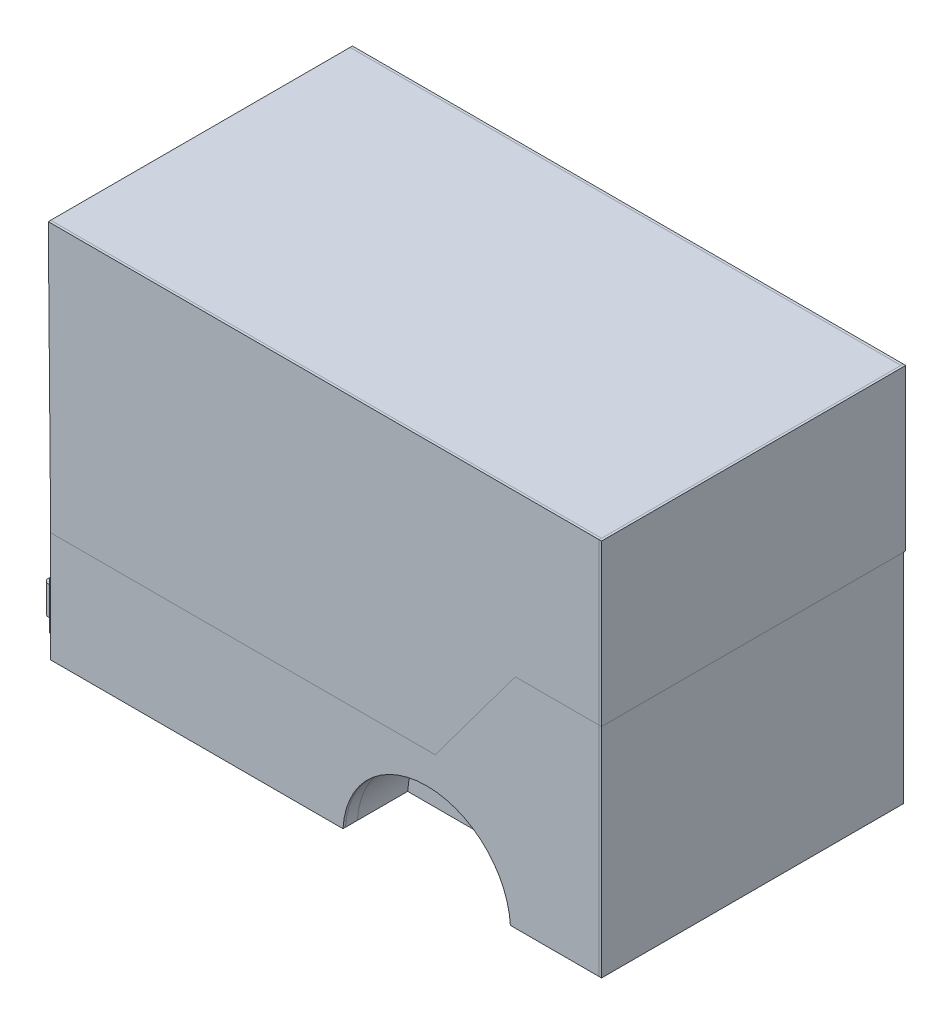
SolidWorks part; units mm, degrees
other "베이스 모듈"
other "결합장치1"
other "측벽"
other "결합장치2"
other "뒷벽인테리어(하양)"
other "뒷벽인테리어(검정)"
other "측벽인테리어(하양)2"
other "측벽인테리어(검정)2"
other "측벽인테리어(검정)1"
other "측벽인테리어(하양)1"
other "뒷벽"
other "천장"
other "뒷면벽"
other "측면벽"
other "침대"
other "베개"
other "이불"
other "싱크대"
other "인덕션"
other "인덕션 불판"
other "인덕션 다이얼"
other "후드"
other "수전"
other "천장수납"
other "천장수납1"
other "천장수납2"
other "천장수납3"
other "천장수납4"
other "부엌싱크"
other "세탁기"
other "세탁기_다이얼"
other "세탁기_스크린_1"
other "세탁기_스크린_2"
other "세탁기 링"
other "냉장고"
other "TV"
other "옷장"
other "탁자"
ref_plane "정면" through (0, 0, 0) normal (0, 0, 1) x (1, 0, 0)
ref_plane "윗면" through (0, 0, 0) normal (0, 1, 0) x (1, 0, 0)
ref_plane "우측면" through (0, 0, 0) normal (1, 0, 0) x (0, 0, -1)
sketch "스케치1" plane through (0, 0, 0) normal (0, 1, 0) x (1, 0, 0)
  line L1 (-757.2313, -2.0205) -> (-986.2313, -2.0205)
  line L2 (-757.2313, -2.0205) -> (-757.2313, -127.0205)
  line L3 (-757.2313, -127.0205) -> (-986.2313, -127.0205)
  line L4 (-986.2313, -2.0205) -> (-986.2313, -127.0205)
extrude "보스-돌출1" add sketch "스케치1" along normal up to surface (88 mm away)
sketch "스케치4" plane through (-986.2313, 0, 0) normal (-1, 0, 0) x (0, 0, 1)
  line L4 (2.0205, 0) -> (127.0205, 0)
  line L5 (2.0205, 88) -> (2.0205, 0)
  line L6 (127.0205, 88) -> (2.0205, 88)
  line L7 (127.0205, 0) -> (127.0205, 88)
  line L8 (123.0205, 84) -> (6.0205, 84)
  line L9 (123.0205, 67.306) -> (123.0205, 84)
  line L10 (120.1014, 42.8854) -> (120.8975, 46.7066)
  line L11 (118.0205, 2) -> (118.0205, 22.694)
  line L12 (11.0205, 2) -> (118.0205, 2)
  line L13 (11.0205, 22.694) -> (11.0205, 2)
  line L14 (8.1434, 46.7066) -> (8.9395, 42.8854)
  line L15 (6.0205, 84) -> (6.0205, 67.306)
  line L16 (123.0205, 84) -> (6.0205, 84)
  line L17 (123.0205, 67.306) -> (123.0205, 84)
  line L18 (120.1014, 42.8854) -> (120.8975, 46.7066)
  line L19 (118.0205, 2) -> (118.0205, 22.694)
  line L20 (11.0205, 2) -> (118.0205, 2)
  line L21 (11.0205, 22.694) -> (11.0205, 2)
  line L22 (8.1434, 46.7066) -> (8.9395, 42.8854)
  line L23 (6.0205, 84) -> (6.0205, 67.306)
  line L24 (117.0205, 3) -> (117.0205, 22.694)
  line L25 (119.1224, 43.0894) -> (119.9185, 46.9106)
  line L26 (122.0205, 67.306) -> (122.0205, 83)
  line L27 (122.0205, 83) -> (7.0205, 83)
  line L28 (7.0205, 83) -> (7.0205, 67.306)
  line L29 (9.1224, 46.9106) -> (9.9185, 43.0894)
  line L30 (12.0205, 22.694) -> (12.0205, 3)
  line L31 (12.0205, 3) -> (117.0205, 3)
  line L32 (117.0205, 3) -> (117.0205, 22.694)
  line L33 (119.1224, 43.0894) -> (119.9185, 46.9106)
  line L34 (122.0205, 67.306) -> (122.0205, 83)
  line L35 (122.0205, 83) -> (7.0205, 83)
  line L36 (7.0205, 83) -> (7.0205, 67.306)
  line L37 (9.1224, 46.9106) -> (9.9185, 43.0894)
  line L38 (12.0205, 22.694) -> (12.0205, 3)
  line L39 (12.0205, 3) -> (117.0205, 3)
  line L40 (2.0205, 0) -> (127.0205, 0)
  line L41 (2.0205, 88) -> (2.0205, 0)
  line L42 (127.0205, 88) -> (2.0205, 88)
  line L43 (127.0205, 0) -> (127.0205, 88)
  line L44 (126.0205, 1) -> (126.0205, 87)
  line L45 (3.0205, 1) -> (126.0205, 1)
  line L46 (3.0205, 87) -> (3.0205, 1)
  line L47 (126.0205, 87) -> (3.0205, 87)
  line L48 (126.0205, 1) -> (126.0205, 87)
  line L49 (3.0205, 1) -> (126.0205, 1)
  line L50 (3.0205, 87) -> (3.0205, 1)
  line L51 (126.0205, 87) -> (3.0205, 87)
  arc A200 (120.8975, 46.7066) -> (123.0205, 67.306) centre (22.0205, 67.306) ccw
  arc A202 (120.8975, 46.7066) -> (123.0205, 67.306) centre (22.0205, 67.306) ccw
  arc A204 (120.1014, 42.8854) -> (118.0205, 22.694) centre (217.0205, 22.694) ccw
  arc A206 (120.1014, 42.8854) -> (118.0205, 22.694) centre (217.0205, 22.694) ccw
  arc A208 (11.0205, 22.694) -> (8.9395, 42.8854) centre (-87.9795, 22.694) ccw
  arc A209 (11.0205, 22.694) -> (8.9395, 42.8854) centre (-87.9795, 22.694) ccw
  arc A210 (6.0205, 67.306) -> (8.1434, 46.7066) centre (107.0205, 67.306) ccw
  arc A211 (6.0205, 67.306) -> (8.1434, 46.7066) centre (107.0205, 67.306) ccw
  arc A212 (119.1224, 43.0894) -> (117.0205, 22.694) centre (217.0205, 22.694) ccw
  arc A213 (119.1224, 43.0894) -> (117.0205, 22.694) centre (217.0205, 22.694) ccw
  arc A214 (119.9185, 46.9106) -> (122.0205, 67.306) centre (22.0205, 67.306) ccw
  arc A215 (119.9185, 46.9106) -> (122.0205, 67.306) centre (22.0205, 67.306) ccw
  arc A216 (7.0205, 67.306) -> (9.1224, 46.9106) centre (107.0205, 67.306) ccw
  arc A217 (7.0205, 67.306) -> (9.1224, 46.9106) centre (107.0205, 67.306) ccw
  arc A218 (12.0205, 22.694) -> (9.9185, 43.0894) centre (-87.9795, 22.694) ccw
  arc A219 (12.0205, 22.694) -> (9.9185, 43.0894) centre (-87.9795, 22.694) ccw
  line M33 (127.0205, 88) -> (2.0205, 88)
  line M34 (2.0205, 88) -> (2.0205, 0)
  line M35 (2.0205, 0) -> (127.0205, 0)
  line M36 (127.0205, 0) -> (127.0205, 88)
  dimension "D1" = 0
  dimension "D2" = 0
  dimension "D3" = 0
  dimension "D4" = 0
extrude "컷-돌출3" cut sketch "스케치4" against normal blind 1 contours L51 L48 L49 L50 M36 M33 M34 M35 | L23 A211 L22 A209 L21 L20 L19 A206 L18 A202 L17 L16 L38 A219 L37 A217 L36 L35 L34 A215 L33 A213 L32 L39 region at (-986.2313, 44, 2.1733) region at (-986.2313, 75.653, 122.8776)
sketch "스케치5" plane through (-757.2313, 0, 0) normal (1, 0, 0) x (0, 0, -1)
  line L4 (-2.0205, 88) -> (-127.0205, 88)
  line L5 (-127.0205, 88) -> (-127.0205, 0)
  line L6 (-127.0205, 0) -> (-2.0205, 0)
  line L7 (-2.0205, 0) -> (-2.0205, 88)
  line L8 (-2.0205, 88) -> (-127.0205, 88)
  line L9 (-127.0205, 88) -> (-127.0205, 0)
  line L10 (-127.0205, 0) -> (-2.0205, 0)
  line L11 (-2.0205, 0) -> (-2.0205, 88)
  dimension "D1" = 0
extrude "보스-돌출2" add sketch "스케치5" along normal blind 1
sketch "스케치11" plane through (-986.2313, 0, 0) normal (-1, 0, 0) x (0, 0, 1)
  line L4 (124.5205, 6) -> (124.5205, 26)
  line L5 (119.5205, 6) -> (124.5205, 6)
  line L6 (119.5205, 26) -> (119.5205, 6)
  line L7 (124.5205, 26) -> (119.5205, 26)
  line L8 (124.5205, 6) -> (124.5205, 26)
  line L9 (119.5205, 6) -> (124.5205, 6)
  line L10 (119.5205, 26) -> (119.5205, 6)
  line L11 (124.5205, 26) -> (119.5205, 26)
  dimension "D1" = 0
extrude "보스-돌출3" add sketch "스케치11" along normal blind 2 separate body
ref_plane "평면2" through (0, 23, 0) normal (0, 1, 0) x (1, 0, 0)
sketch "스케치12" plane through (0, 23, 0) normal (0, 1, 0) x (1, 0, 0)
  line L0 (-988.2313, -124.5205) -> (-986.2313, -124.5205) construction
  line L1 (-988.2313, -124.5205) -> (-988.2313, -119.5205) construction
  circle A0 centre (-989.2313, -122.0205) radius 2
  dimension "D1" = 4
  dimension "D2" = 2.5
  dimension "D3" = 1
extrude "보스-돌출4" add sketch "스케치12" against normal blind 12
ref_plane "평면3" through (0, 0, 64.5205) normal (0, 0, 1) x (1, 0, 0)
mirror "대칭 복사1" about plane through (0, 0, 64.5205) normal (0, 0, 1) of bodies 111
sketch "스케치13" plane through (0, 0, 127.0205) normal (0, 0, 1) x (1, 0, 0)
  circle A0 centre (-827.2313, -2) radius 35
  dimension "D1" = 70
extrude "컷-돌출7" cut sketch "스케치13" against normal blind 26
sketch "스케치14" plane through (0, 0, 2.0205) normal (0, 0, -1) x (-1, 0, 0)
  circle A0 centre (827.2313, -2) radius 35
  dimension "D1" = 70
extrude "컷-돌출8" cut sketch "스케치14" against normal blind 26
sketch "스케치16" plane through (0, 88, 0) normal (0, 1, 0) x (1, 0, 0)
  line L4 (-756.2313, -2.0205) -> (-985.2313, -2.0205)
  line L5 (-985.2313, -2.0205) -> (-985.2313, -127.0205)
  line L6 (-985.2313, -127.0205) -> (-756.2313, -127.0205)
  line L7 (-756.2313, -127.0205) -> (-756.2313, -2.0205)
  line L8 (-756.2313, -2.0205) -> (-985.2313, -2.0205)
  line L9 (-985.2313, -2.0205) -> (-985.2313, -127.0205)
  line L10 (-985.2313, -127.0205) -> (-756.2313, -127.0205)
  line L11 (-756.2313, -127.0205) -> (-756.2313, -2.0205)
  dimension "D1" = 0
extrude "보스-돌출6" add sketch "스케치16" along normal blind 70
shell "쉘1" thickness 5 removed face at (-756.2313, 79, 64.5205)
sketch "스케치18" plane through (-981.2313, 0, 0) normal (1, 0, 0) x (0, 0, -1)
  line L8 (-17.0205, 8) -> (-17.0205, 22.694)
  line L9 (-14.8134, 44.1092) -> (-14.0173, 47.9304)
  line L10 (-12.0205, 67.306) -> (-12.0205, 78)
  line L11 (-12.0205, 78) -> (-117.0205, 78)
  line L12 (-117.0205, 78) -> (-117.0205, 67.306)
  line L13 (-115.0236, 47.9304) -> (-114.2275, 44.1092)
  line L14 (-112.0205, 22.694) -> (-112.0205, 8)
  line L15 (-112.0205, 8) -> (-17.0205, 8)
  line L16 (-17.0205, 8) -> (-17.0205, 22.694)
  line L17 (-14.8134, 44.1092) -> (-14.0173, 47.9304)
  line L18 (-12.0205, 67.306) -> (-12.0205, 78)
  line L19 (-12.0205, 78) -> (-117.0205, 78)
  line L20 (-117.0205, 78) -> (-117.0205, 67.306)
  line L21 (-115.0236, 47.9304) -> (-114.2275, 44.1092)
  line L22 (-112.0205, 22.694) -> (-112.0205, 8)
  line L23 (-112.0205, 8) -> (-17.0205, 8)
  arc A4 (-14.8134, 44.1092) -> (-17.0205, 22.694) centre (87.9795, 22.694) ccw
  arc A5 (-14.0173, 47.9304) -> (-12.0205, 67.306) centre (-107.0205, 67.306) ccw
  arc A6 (-117.0205, 67.306) -> (-115.0236, 47.9304) centre (-22.0205, 67.306) ccw
  arc A7 (-112.0205, 22.694) -> (-114.2275, 44.1092) centre (-217.0205, 22.694) ccw
  arc A8 (-14.8134, 44.1092) -> (-17.0205, 22.694) centre (87.9795, 22.694) ccw
  arc A9 (-14.0173, 47.9304) -> (-12.0205, 67.306) centre (-107.0205, 67.306) ccw
  arc A10 (-117.0205, 67.306) -> (-115.0236, 47.9304) centre (-22.0205, 67.306) ccw
  arc A11 (-112.0205, 22.694) -> (-114.2275, 44.1092) centre (-217.0205, 22.694) ccw
  dimension "D1" = 0
extrude "컷-돌출9" cut sketch "스케치18" against normal blind 70
sketch "스케치20" plane through (-756.2313, 0, 0) normal (1, 0, 0) x (0, 0, -1)
  line L4 (-127.0205, 0) -> (-2.0205, 0)
  line L5 (-2.0205, 0) -> (-2.0205, 158)
  line L6 (-2.0205, 158) -> (-127.0205, 158)
  line L7 (-127.0205, 158) -> (-127.0205, 0)
  line L8 (-127.0205, 0) -> (-2.0205, 0)
  line L9 (-2.0205, 0) -> (-2.0205, 158)
  line L10 (-2.0205, 158) -> (-127.0205, 158)
  line L11 (-127.0205, 158) -> (-127.0205, 0)
  line L12 (-122.0205, 153) -> (-122.0205, 5)
  line L13 (-122.0205, 5) -> (-7.0205, 5)
  line L14 (-7.0205, 5) -> (-7.0205, 153)
  line L15 (-7.0205, 153) -> (-122.0205, 153)
  line L16 (-122.0205, 153) -> (-122.0205, 5)
  line L17 (-122.0205, 5) -> (-7.0205, 5)
  line L18 (-7.0205, 5) -> (-7.0205, 153)
  line L19 (-7.0205, 153) -> (-122.0205, 153)
  dimension "D1" = 0
  dimension "D2" = 0
extrude "보스-돌출7" add sketch "스케치20" along normal blind 1
sketch "스케치24" plane through (0, 0, 127.0205) normal (0, 0, 1) x (1, 0, 0)
  line L0 (-755.2313, 158) -> (-755.2313, 0) construction
  line L1 (-755.2313, 153) -> (-980.2313, 153)
  line L2 (-755.2313, 153) -> (-755.2313, 5)
  line L3 (-755.2313, 5) -> (-787.8486, 5)
  line L4 (-980.2313, 153) -> (-980.2313, 5)
  line L5 (-985.2313, 158) -> (-755.2313, 158) construction
  line L6 (-792.2885, 0) -> (-755.2313, 0) construction
  line L7 (-985.2313, 0) -> (-985.2313, 158) construction
  line L8 (-866.6141, 5) -> (-980.2313, 5)
  arc A0 (-787.8486, 5) -> (-866.6141, 5) centre (-827.2313, -2) ccw
  arc M2 (-862.1741, 0) -> (-792.2885, 0) centre (-827.2313, -2) cw
  line M4 (-755.2313, 0) -> (-755.2313, 158)
  dimension "D4" = 80
  dimension "D1" = 5
  dimension "D2" = 5
  dimension "D3" = 5
extrude "컷-돌출14" cut sketch "스케치24" against normal up to surface (5 mm away) contours L8 L3 L1 L4 M2 M4 region at (-870.2589, 82.756, 127.0205)
sketch "스케치25" plane through (0, 0, 127.0205) normal (0, 0, 1) x (1, 0, 0)
  line L0 (-857.2313, -2) -> (-796.7667, -2) construction
  line L1 (-980.2313, 153) -> (-755.2313, 153)
  line L2 (-980.2313, 153) -> (-980.2313, 5)
  line L3 (-980.2313, 5) -> (-866.3818, 5)
  line L4 (-755.2313, 153) -> (-755.2313, 5)
  line L5 (-787.6163, 5) -> (-755.2313, 5)
  arc A0 (-787.6163, 5) -> (-866.3818, 5) centre (-826.999, -2) ccw
  dimension "D1" = 80
extrude "보스-돌출8" add sketch "스케치25" against normal blind 5 separate body
sketch "스케치26" plane through (0, 158, 0) normal (0, 1, 0) x (1, 0, 0)
  line L1 (-985.2313, -2.0205) -> (-755.2313, -2.0205)
  line L2 (-985.2313, -2.0205) -> (-985.2313, -127.0205)
  line L3 (-985.2313, -127.0205) -> (-755.2313, -127.0205)
  line L4 (-755.2313, -2.0205) -> (-755.2313, -127.0205)
extrude "컷-돌출15" cut sketch "스케치26" against normal blind 5
sketch "스케치27" plane through (0, 153, 0) normal (0, 1, 0) x (1, 0, 0)
  line L1 (-985.2313, -2.0205) -> (-755.2313, -2.0205)
  line L2 (-985.2313, -2.0205) -> (-985.2313, -127.0205)
  line L3 (-985.2313, -127.0205) -> (-755.2313, -127.0205)
  line L4 (-755.2313, -2.0205) -> (-755.2313, -127.0205)
extrude "보스-돌출9" add sketch "스케치27" along normal blind 5 separate body
sketch "스케치28" plane through (0, 5, 0) normal (0, 1, 0) x (1, 0, 0)
  line L1 (-755.2313, -7.0205) -> (-760.2313, -7.0205)
  line L2 (-755.2313, -7.0205) -> (-755.2313, -122.0205)
  line L3 (-755.2313, -122.0205) -> (-760.2313, -122.0205)
  line L4 (-760.2313, -7.0205) -> (-760.2313, -122.0205)
  dimension "D1" = 5
extrude "보스-돌출10" add sketch "스케치28" along normal up to surface (148 mm away) separate body up to face at (-870.2313, 153, 64.5205)
sketch "스케치29" plane through (0, 0, 2.0205) normal (0, 0, -1) x (-1, 0, 0)
  line L0 (984.2313, 0) -> (984.2313, 88) construction
  line L1 (984.2313, 46) -> (823.6551, 46)
  line L2 (984.2313, 46) -> (984.2313, 0)
  line L3 (984.2313, 0) -> (862.1741, 0)
  line L5 (792.2885, 0) -> (755.2313, 0)
  line L6 (755.2313, 90.9094) -> (790.2313, 90.9094)
  line L7 (755.2313, 0) -> (755.2313, 153) construction
  line L8 (790.2313, 90.9094) -> (823.6551, 46)
  line L9 (755.2313, 90.9094) -> (755.2313, 0)
  arc A0 (862.1741, 0) -> (792.2885, 0) centre (827.2313, -2) ccw
  line M6 (755.2313, 153) -> (755.2313, 0)
  line M7 (755.2313, 0) -> (792.2885, 0)
  arc M8 (792.2885, 0) -> (862.1741, 0) centre (827.2313, -2) cw
  line M9 (862.1741, 0) -> (985.2313, 0)
  dimension "D1" = 35
extrude "보스-돌출11" add sketch "스케치29" along normal blind 1 separate body contours L8 L6 L2 L1 M6 M7 M8 M9 region at (-858.1762, 33.4866, 2.0205)
sketch "스케치30" plane through (0, 0, 2.0205) normal (0, 0, -1) x (-1, 0, 0)
  line L0 (755.2313, 90.9094) -> (755.2313, 158)
  line L1 (755.2313, 158) -> (985.2313, 158)
  line L2 (985.2313, 158) -> (984.2313, 46)
  line L3 (984.2313, 46) -> (823.6551, 46)
  line L4 (984.2313, 46) -> (823.6551, 46) construction
  line L5 (823.6551, 46) -> (790.2313, 90.9094)
  line L6 (790.2313, 90.9094) -> (755.2313, 90.9094)
extrude "보스-돌출12" add sketch "스케치30" along normal blind 1 separate body
delete or keep bodies "바디-삭제/보존 2" type delete bodies bodies 112
ref_plane "평면5" through (0, 0, 64.5205) normal (0, 0, 1) x (1, 0, 0)
mirror "대칭 복사3" about plane through (0, 0, 64.5205) normal (0, 0, 1) of bodies 131 130
sketch "스케치32" plane through (-755.2313, 0, 0) normal (1, 0, 0) x (0, 0, -1)
  line L1 (-128.0205, 90.9094) -> (-1.0205, 90.9094)
  line L2 (-128.0205, 90.9094) -> (-128.0205, 158)
  line L3 (-128.0205, 158) -> (-1.0205, 158)
  line L4 (-1.0205, 90.9094) -> (-1.0205, 158)
extrude "보스-돌출13" add sketch "스케치32" along normal blind 1 separate body
sketch "스케치33" plane through (-755.2313, 0, 0) normal (1, 0, 0) x (0, 0, -1)
  line L1 (-128.0205, 90.9094) -> (-2.0205, 90.9094)
  line L2 (-128.0205, 90.9094) -> (-128.0205, 0)
  line L3 (-128.0205, 0) -> (-2.0205, 0)
  line L4 (-2.0205, 90.9094) -> (-2.0205, 0)
extrude "보스-돌출14" add sketch "스케치33" along normal blind 1 separate body
mirror "대칭 복사4" about plane through (0, 0, 64.5205) normal (0, 0, 1) of bodies 111
delete or keep bodies "바디-삭제/보존 3" type delete bodies bodies 126
sketch "스케치34" plane through (0, 5, 0) normal (0, 1, 0) x (1, 0, 0)
  line L1 (-980.2313, -127.0205) -> (-755.2313, -127.0205)
  line L2 (-980.2313, -127.0205) -> (-980.2313, -122.0205)
  line L3 (-980.2313, -122.0205) -> (-755.2313, -122.0205)
  line L4 (-755.2313, -127.0205) -> (-755.2313, -122.0205)
extrude "컷-돌출16" cut sketch "스케치34" against normal blind 10 and the other way blind 40
sketch "스케치35" plane through (0, 0, 122.0205) normal (0, 0, 1) x (1, 0, 0)
  line L0 (-980.2313, 0) -> (-760.2313, 0)
  line L2 (-980.2313, 0) -> (-980.2313, 153)
  line L3 (-980.2313, 153) -> (-760.2313, 153)
  line L4 (-760.2313, 0) -> (-760.2313, 153)
extrude "보스-돌출16" add sketch "스케치35" along normal blind 5 separate body
sketch "스케치36" plane through (-760.2313, 0, 0) normal (1, 0, 0) x (0, 0, -1)
  line L4 (-122.0205, 0) -> (-122.0205, 153)
  line L5 (-122.0205, 153) -> (-127.0205, 153)
  line L6 (-127.0205, 153) -> (-127.0205, 0)
  line L7 (-127.0205, 0) -> (-122.0205, 0)
  line L8 (-122.0205, 0) -> (-122.0205, 153)
  line L9 (-122.0205, 153) -> (-127.0205, 153)
  line L10 (-127.0205, 153) -> (-127.0205, 0)
  line L11 (-127.0205, 0) -> (-122.0205, 0)
  dimension "D1" = 0
extrude "보스-돌출17" add sketch "스케치36" along normal up to surface (5 mm away) up to face at (-755.2313, 124.4547, 64.5205)
sketch "스케치37" plane through (0, 0, 127.0205) normal (0, 0, 1) x (1, 0, 0)
  line L1 (-862.1741, 0) -> (-792.2885, 0)
  line L2 (-862.1741, 0) -> (-792.2885, 0)
  arc A1 (-792.2885, 0) -> (-862.1741, 0) centre (-827.2313, -2) ccw
  arc A2 (-792.2885, 0) -> (-862.1741, 0) centre (-827.2313, -2) ccw
  dimension "D1" = 0
extrude "컷-돌출17" cut sketch "스케치37" against normal blind 5
delete or keep bodies "바디-삭제/보존 4" type delete bodies bodies 129
sketch "스케치39" plane through (-755.2313, 0, 0) normal (1, 0, 0) x (0, 0, -1)
  line L0 (-122.0205, 5) -> (-122.0205, 0) construction
  line L1 (-7.0205, 5) -> (-122.0205, 5)
  line L2 (-7.0205, 5) -> (-7.0205, 0)
  line L3 (-7.0205, 0) -> (-122.0205, 0)
  line L4 (-122.0205, 5) -> (-122.0205, 0)
  line L5 (-122.0205, 0) -> (-2.0205, 0) construction
extrude "컷-돌출18" cut sketch "스케치39" against normal blind 5
sketch "스케치40" plane through (0, 0, 0) normal (0, -1, 0) x (1, 0, 0)
  line L1 (-760.2313, 7.0205) -> (-755.2313, 7.0205)
  line L2 (-760.2313, 7.0205) -> (-760.2313, 127.0205)
  line L3 (-760.2313, 127.0205) -> (-755.2313, 127.0205)
  line L4 (-755.2313, 7.0205) -> (-755.2313, 127.0205)
  dimension "D1" = 120
extrude "보스-돌출19" add sketch "스케치40" against normal up to surface (153 mm away) separate body up to face at (-870.2313, 153, 64.5205)
sketch "스케치45" plane through (0, 5, 0) normal (0, 1, 0) x (1, 0, 0)
  line L1 (-866.6141, -7.0205) -> (-787.8486, -7.0205)
  line L2 (-866.6141, -7.0205) -> (-866.6141, -33.0205)
  line L3 (-866.6141, -33.0205) -> (-787.8486, -33.0205)
  line L4 (-787.8486, -7.0205) -> (-787.8486, -33.0205)
  line L5 (-866.6141, -122.0205) -> (-787.8486, -122.0205)
  line L6 (-866.6141, -122.0205) -> (-866.6141, -96.0205)
  line L7 (-866.6141, -96.0205) -> (-787.8486, -96.0205)
  line L8 (-787.8486, -122.0205) -> (-787.8486, -96.0205)
extrude "보스-돌출21" add sketch "스케치45" along normal blind 33
sketch "스케치47" plane through (0, 0, 122.0205) normal (0, 0, 1) x (1, 0, 0)
  line L0 (-862.1741, 0) -> (-792.2885, 0) construction
  line L1 (-862.1741, 0) -> (-792.2885, 0)
  arc A0 (-792.2885, 0) -> (-862.1741, 0) centre (-827.2313, -2) ccw construction
  arc A1 (-792.2885, 0) -> (-862.1741, 0) centre (-827.2313, -2) ccw
extrude "컷-돌출20" cut sketch "스케치47" against normal blind 21
sketch "스케치48" plane through (0, 0, 7.0205) normal (0, 0, -1) x (-1, 0, 0)
  circle A0 centre (827.2523, -1.9146) radius 34.912
extrude "컷-돌출21" cut sketch "스케치48" against normal blind 21
sketch "스케치51" plane through (0, 5, 0) normal (0, 1, 0) x (1, 0, 0)
  line L1 (-760.2313, -122.0205) -> (-880.2313, -122.0205)
  line L2 (-760.2313, -122.0205) -> (-760.2313, -72.0205)
  line L3 (-760.2313, -72.0205) -> (-880.2313, -72.0205)
  line L4 (-880.2313, -122.0205) -> (-880.2313, -72.0205)
  dimension "D1" = 50
  dimension "D2" = 120
extrude "보스-돌출22" add sketch "스케치51" along normal blind 35 separate body
sketch "스케치53" plane through (0, 0, 122.0205) normal (0, 0, 1) x (1, 0, 0)
  line L3 (-866.6141, 5) -> (-787.8486, 5)
  line L9 (-792.2885, 0) -> (-760.2313, 0)
  line L10 (-760.2313, 0) -> (-760.2313, 5)
  line L11 (-760.2313, 5) -> (-787.8486, 5)
  line L12 (-787.8486, 5) -> (-787.8486, 38)
  line L13 (-787.8486, 38) -> (-866.6141, 38)
  line L14 (-866.6141, 38) -> (-866.6141, 5)
  line L16 (-980.2313, 5) -> (-980.2313, 0)
  line L17 (-980.2313, 0) -> (-862.1741, 0)
  line L21 (-787.8486, 5) -> (-787.8486, 38)
  line L22 (-787.8486, 38) -> (-866.6141, 38)
  line L23 (-866.6141, 38) -> (-866.6141, 5)
  line L31 (-866.6141, 5) -> (-980.2313, 5)
  circle A0 centre (-815.4825, 30.9843) radius 0.0143
  arc A2 (-792.2885, 0) -> (-862.1741, 0) centre (-827.2313, -2) ccw
  dimension "D1" = 0
extrude "컷-돌출22" cut sketch "스케치53" against normal blind 26
sketch "스케치55" plane through (0, 40, 0) normal (0, 1, 0) x (1, 0, 0)
  line L0 (-760.2313, -72.0205) -> (-880.2313, -72.0205) construction
  line L1 (-784.2313, -84.5205) -> (-769.2313, -84.5205)
  line L2 (-784.2313, -84.5205) -> (-784.2313, -109.5205)
  line L3 (-784.2313, -109.5205) -> (-769.2313, -109.5205)
  line L4 (-769.2313, -84.5205) -> (-769.2313, -109.5205)
  line L5 (-760.2313, -122.0205) -> (-760.2313, -72.0205) construction
  dimension "D1" = 25
  dimension "D2" = 15
  dimension "D3" = 12.5
  dimension "D4" = 9
extrude "보스-돌출23" add sketch "스케치55" along normal blind 10 separate body
fillet "필렛1" radius 5 4 edges at (-784.2313, 50, 97.0205) (-776.7313, 50, 109.5205) (-769.2313, 50, 97.0205) (-776.7313, 50, 84.5205) type face fillet first side face at (-776.7313, 50, 97.0205) second side face at (-776.7313, 45, 84.5205) second side face at (-769.2313, 45, 97.0205) second side face at (-776.7313, 45, 109.5205) second side face at (-784.2313, 45, 97.0205)
sketch "스케치56" plane through (0, 40, 0) normal (0, 1, 0) x (1, 0, 0)
  line L0 (-760.2313, -72.0205) -> (-880.2313, -72.0205) construction
  line L1 (-880.2313, -122.0205) -> (-790.2313, -122.0205)
  line L2 (-880.2313, -122.0205) -> (-880.2313, -65.0205)
  line L3 (-880.2313, -65.0205) -> (-790.2313, -65.0205)
  line L4 (-790.2313, -122.0205) -> (-790.2313, -65.0205)
  dimension "D1" = 90
  dimension "D2" = 7
extrude "보스-돌출24" add sketch "스케치56" along normal blind 7 separate body
sketch "스케치57" plane through (0, 40, 0) normal (0, -1, 0) x (1, 0, 0)
  line L1 (-790.2313, 65.0205) -> (-880.2313, 65.0205)
  line L2 (-790.2313, 65.0205) -> (-790.2313, 72.0205)
  line L3 (-790.2313, 72.0205) -> (-880.2313, 72.0205)
  line L4 (-880.2313, 65.0205) -> (-880.2313, 72.0205)
extrude "보스-돌출25" add sketch "스케치57" along normal blind 17
fillet "필렛2" radius 5 1 edges at (-835.2313, 47, 65.0205) type face fillet first side face at (-835.2313, 35, 65.0205) second side face at (-835.2313, 47, 93.5205)
fillet "필렛3" radius 5 1 edges at (-835.2313, 23, 65.0205) type face fillet first side face at (-835.2313, 23, 68.5205) second side face at (-835.2313, 32.5, 65.0205)
fillet "필렛4" radius 5 1 edges at (-790.2313, 47, 96.0205) type face fillet first side face at (-835.2313, 47, 96.0205) second side face at (-790.2313, 36.25, 82.0116)
sketch "스케치58" plane through (0, 5, 0) normal (0, 1, 0) x (1, 0, 0)
  line L0 (-866.6141, -7.0205) -> (-980.2313, -7.0205) construction
  line L1 (-880.2313, -7.0205) -> (-760.2313, -7.0205)
  line L2 (-880.2313, -7.0205) -> (-880.2313, -33.0205)
  line L3 (-880.2313, -33.0205) -> (-760.2313, -33.0205)
  line L4 (-760.2313, -7.0205) -> (-760.2313, -33.0205)
  line L5 (-760.2313, -7.0205) -> (-760.2313, -122.0205) construction
extrude "보스-돌출26" add sketch "스케치58" along normal blind 47 separate body
sketch "스케치59" plane through (0, 0, 33.0205) normal (0, 0, 1) x (1, 0, 0)
  line L1 (-866.6141, 5) -> (-787.8486, 5)
  line L2 (-866.6141, 5) -> (-866.6141, 38)
  line L3 (-866.6141, 38) -> (-787.8486, 38)
  line L4 (-787.8486, 5) -> (-787.8486, 38)
  line M5 (-880.2313, 5) -> (-760.2313, 5)
extrude "컷-돌출24" cut sketch "스케치59" against normal up to surface (26 mm away) contours L4 L3 L2 M5 region at (-827.2313, 21.5, 33.0205)
sketch "스케치60" plane through (0, 0, 33.0205) normal (0, 0, 1) x (1, 0, 0)
  line L1 (-880.2313, 52) -> (-760.2313, 52)
  line L2 (-880.2313, 52) -> (-880.2313, 5)
  line L3 (-880.2313, 5) -> (-760.2313, 5)
  line L4 (-760.2313, 52) -> (-760.2313, 5)
extrude "보스-돌출27" add sketch "스케치60" along normal blind 5
sketch "스케치61" plane through (0, 52, 0) normal (0, 1, 0) x (1, 0, 0)
  line L0 (-760.2313, -38.0205) -> (-880.2313, -38.0205) construction
  line L1 (-760.2313, -7.0205) -> (-790.2313, -7.0205)
  line L2 (-760.2313, -7.0205) -> (-760.2313, -38.0205)
  line L3 (-760.2313, -38.0205) -> (-790.2313, -38.0205)
  line L4 (-790.2313, -7.0205) -> (-790.2313, -38.0205)
  dimension "D1" = 30
extrude "보스-돌출28" add sketch "스케치61" along normal blind 4 separate body
sketch "스케치62" plane through (0, 56, 0) normal (0, 1, 0) x (1, 0, 0)
  line L0 (-760.2313, -7.0205) -> (-790.2313, -7.0205) construction
  circle A0 centre (-775.2313, -18.0205) radius 9
  dimension "D2" = 18
  dimension "D1" = 11
extrude "보스-돌출29" add sketch "스케치62" along normal blind 1 separate body
sketch "스케치63" plane through (0, 56, 0) normal (0, 1, 0) x (1, 0, 0)
  line L0 (-790.2313, -38.0205) -> (-760.2313, -38.0205) construction
  line L1 (-787.2313, -33.0205) -> (-774.2313, -33.0205)
  line L2 (-787.2313, -33.0205) -> (-787.2313, -37.0205)
  line L3 (-787.2313, -37.0205) -> (-774.2313, -37.0205)
  line L4 (-774.2313, -33.0205) -> (-774.2313, -37.0205)
  line L5 (-790.2313, -7.0205) -> (-790.2313, -38.0205) construction
  dimension "D1" = 13
  dimension "D2" = 4
  dimension "D3" = 1
  dimension "D4" = 3
extrude "컷-돌출25" cut sketch "스케치63" against normal blind 1
sketch "스케치64" plane through (0, 56, 0) normal (0, 1, 0) x (1, 0, 0)
  circle A0 centre (-766.3695, -34.4167) radius 2.5
  dimension "D1" = 5
extrude "보스-돌출30" add sketch "스케치64" along normal blind 1 separate body
sketch "스케치65" plane through (0, 0, 7.0205) normal (0, 0, 1) x (1, 0, 0)
  line L0 (-755.2313, 153) -> (-980.2313, 153) construction
  line L1 (-760.2313, 153) -> (-790.2313, 153)
  line L2 (-760.2313, 153) -> (-760.2313, 108)
  line L3 (-760.2313, 108) -> (-790.2313, 108)
  line L4 (-790.2313, 153) -> (-790.2313, 108)
  dimension "D1" = 45
  dimension "D2" = 30
extrude "보스-돌출31" add sketch "스케치65" along normal blind 31 separate body
fillet "필렛5" radius 30 1 edges at (-775.2313, 153, 38.0205) type face fillet first side face at (-775.2313, 130.5, 38.0205) second side face at (-775.2313, 153, 22.5205)
sketch "스케치67" plane through (0, 108, 0) normal (0, -1, 0) x (1, 0, 0)
  line L4 (-790.2313, 7.0205) -> (-760.2313, 7.0205)
  line L5 (-760.2313, 7.0205) -> (-760.2313, 38.0205)
  line L6 (-760.2313, 38.0205) -> (-790.2313, 38.0205)
  line L7 (-790.2313, 38.0205) -> (-790.2313, 7.0205)
  line L8 (-790.2313, 7.0205) -> (-760.2313, 7.0205)
  line L9 (-760.2313, 7.0205) -> (-760.2313, 38.0205)
  line L10 (-760.2313, 38.0205) -> (-790.2313, 38.0205)
  line L11 (-790.2313, 38.0205) -> (-790.2313, 7.0205)
  dimension "D1" = 0
extrude "보스-돌출32" add sketch "스케치67" along normal blind 10
sketch "스케치68" plane through (0, 52, 0) normal (0, 1, 0) x (1, 0, 0)
  line L0 (-760.2313, -38.0205) -> (-880.2313, -38.0205) construction
  line L3 (-866.4296, -26.0205) -> (-846.4296, -26.0205) construction
  line L4 (-866.4296, -17.0205) -> (-846.4296, -17.0205)
  line L5 (-866.4296, -35.0205) -> (-846.4296, -35.0205)
  arc A0 (-866.4296, -17.0205) -> (-866.4296, -35.0205) centre (-866.4296, -26.0205) ccw
  arc A1 (-846.4296, -35.0205) -> (-846.4296, -17.0205) centre (-846.4296, -26.0205) ccw
  point P8 (-856.4296, -26.0205)
  dimension "D1" = 18
  dimension "D2" = 20
  dimension "D3" = 3
extrude "컷-돌출27" cut sketch "스케치68" against normal blind 13 draft 12
sketch "스케치69" plane through (0, 52, 0) normal (0, 1, 0) x (1, 0, 0)
  line L0 (-866.4296, -17.0205) -> (-846.4296, -17.0205) construction
  line L1 (-856.4296, -17.0205) -> (-856.4296, -7.0205) construction
  line L2 (-760.2313, -7.0205) -> (-880.2313, -7.0205) construction
  circle A0 centre (-856.4296, -12.0205) radius 1.5
  dimension "D1" = 3
ref_plane "평면6" through (-856.4296, 0, 0) normal (1, 0, 0) x (0, 0, -1)
sketch "스케치70" plane through (-856.4296, 0, 0) normal (1, 0, 0) x (0, 0, -1)
  line L0 (-17.0205, 52) -> (-17.0205, 59.7915) construction
  line L2 (-12.0375, 52) -> (-12.0375, 59.7915)
  arc A1 (-12.0375, 59.7915) -> (-22.0034, 59.7915) centre (-17.0205, 59.7915) ccw
  point P3 (-17.0205, 55.8957)
extrude "보스-돌출33" add sketch "스케치69" along normal blind 1 separate body
sketch "스케치71" plane through (0, 53, 0) normal (0, 1, 0) x (1, 0, 0)
  circle A1 centre (-856.4296, -12.0205) radius 1.5
  circle A2 centre (-856.4296, -12.0205) radius 1.5
  dimension "D1" = 0
sweep "스윕2" add profiles "스케치71" path "스케치70"
sketch "스케치72" plane through (0, 0, 7.0205) normal (0, 0, 1) x (1, 0, 0)
  line L0 (-755.2313, 153) -> (-980.2313, 153) construction
  line L1 (-880.2313, 153) -> (-792.2313, 153)
  line L2 (-880.2313, 153) -> (-880.2313, 98)
  line L3 (-880.2313, 98) -> (-792.2313, 98)
  line L4 (-792.2313, 153) -> (-792.2313, 98)
  dimension "D1" = 88
extrude "보스-돌출34" add sketch "스케치72" along normal up to surface (31 mm away) separate body up to face at (-775.2313, 110.5, 38.0205)
sketch "스케치73" plane through (0, 0, 38.0205) normal (0, 0, 1) x (1, 0, 0)
  line L0 (-880.2313, 153) -> (-792.2313, 153) construction
  line L1 (-858.2313, 153) -> (-858.2313, 98)
  line L2 (-792.2313, 98) -> (-880.2313, 98) construction
  line L3 (-880.2313, 98) -> (-880.2313, 153) construction
  line L4 (-836.2313, 153) -> (-836.2313, 98)
  line L5 (-814.2313, 153) -> (-814.2313, 98)
  dimension "D1" = 22
  dimension "D2" = 3
sketch "스케치74" plane through (0, 153, 0) normal (0, 1, 0) x (1, 0, 0)
  line L0 (-880.2313, -38.0205) -> (-792.2313, -38.0205) construction
  line L1 (-880.2313, -38.0205) -> (-880.2313, -7.0205) construction
  line L2 (-859.2313, -38.0205) -> (-858.2313, -38.0205)
  line L3 (-858.2313, -38.0205) -> (-858.2313, -37.0205)
  line L4 (-836.2313, -38.0205) -> (-836.2313, -37.0205)
  line L5 (-837.2313, -38.0205) -> (-836.2313, -38.0205)
  line L6 (-814.2313, -38.0205) -> (-814.2313, -37.0205)
  line L7 (-815.2313, -38.0205) -> (-814.2313, -38.0205)
  line L8 (-792.2313, -38.0205) -> (-792.2313, -37.0205)
  line L9 (-793.2313, -38.0205) -> (-792.2313, -38.0205)
  arc A0 (-859.2313, -38.0205) -> (-858.2313, -37.0205) centre (-858.2313, -38.0205) cw
  arc A1 (-837.2313, -38.0205) -> (-836.2313, -37.0205) centre (-836.2313, -38.0205) cw
  arc A2 (-815.2313, -38.0205) -> (-814.2313, -37.0205) centre (-814.2313, -38.0205) cw
  arc A3 (-793.2313, -38.0205) -> (-792.2313, -37.0205) centre (-792.2313, -38.0205) cw
  point P0 (-858.2313, -38.0205)
  point P1 (-836.2313, -38.0205)
  point P6 (-814.2313, -38.0205)
  dimension "D3" = 1
  dimension "D1" = 22
  dimension "D2" = 3
  dimension "D4" = 4
extrude "컷-돌출28" cut sketch "스케치74" against normal up to surface (55 mm away) up to face at (-836.2313, 98, 22.5205)
sketch "스케치75" plane through (0, 153, 0) normal (0, 1, 0) x (1, 0, 0)
  line L0 (-792.2313, -7.0205) -> (-880.2313, -7.0205) construction
  line L1 (-858.2313, -38.0205) -> (-859.2313, -38.0205)
  line L2 (-858.2313, -38.0205) -> (-858.2313, -7.0205)
  line L3 (-858.2313, -7.0205) -> (-859.2313, -7.0205)
  line L4 (-859.2313, -38.0205) -> (-859.2313, -7.0205)
  line L5 (-836.2313, -38.0205) -> (-837.2313, -38.0205)
  line L6 (-836.2313, -38.0205) -> (-836.2313, -7.0205)
  line L7 (-836.2313, -7.0205) -> (-837.2313, -7.0205)
  line L8 (-837.2313, -38.0205) -> (-837.2313, -7.0205)
  line L9 (-814.2313, -38.0205) -> (-815.2313, -38.0205)
  line L10 (-814.2313, -38.0205) -> (-814.2313, -7.0205)
  line L11 (-814.2313, -7.0205) -> (-815.2313, -7.0205)
  line L12 (-815.2313, -38.0205) -> (-815.2313, -7.0205)
  line L13 (-792.2313, -38.0205) -> (-793.2313, -38.0205)
  line L14 (-792.2313, -38.0205) -> (-792.2313, -7.0205)
  line L15 (-792.2313, -7.0205) -> (-793.2313, -7.0205)
  line L16 (-793.2313, -38.0205) -> (-793.2313, -7.0205)
  dimension "D1" = 1
  dimension "D2" = 4
extrude "컷-돌출29" cut sketch "스케치75" against normal up to surface (55 mm away) up to face at (-833.4333, 98, 33.247)
sketch "스케치76" plane through (0, 153, 0) normal (0, 1, 0) x (1, 0, 0)
  line L0 (-880.2313, -38.0205) -> (-859.2313, -38.0205) construction
  line L1 (-860.7313, -38.0205) -> (-859.7313, -38.0205)
  line L2 (-838.7313, -38.0205) -> (-837.7313, -38.0205)
  line L3 (-816.7313, -38.0205) -> (-815.7313, -38.0205)
  line L4 (-794.7313, -38.0205) -> (-793.7313, -38.0205)
  arc A0 (-860.7313, -38.0205) -> (-859.7313, -38.0205) centre (-860.2313, -38.0205) cw
  arc A1 (-838.7313, -38.0205) -> (-837.7313, -38.0205) centre (-838.2313, -38.0205) cw
  arc A2 (-816.7313, -38.0205) -> (-815.7313, -38.0205) centre (-816.2313, -38.0205) cw
  arc A3 (-794.7313, -38.0205) -> (-793.7313, -38.0205) centre (-794.2313, -38.0205) cw
  dimension "D1" = 0.5
  dimension "D2" = 0.5
  dimension "D3" = 4
extrude "컷-돌출30" cut sketch "스케치76" against normal up to surface (55 mm away) up to face at (-869.7313, 98, 22.5205)
sketch "스케치77" plane through (0, 0, 38.0205) normal (0, 0, 1) x (1, 0, 0)
  line L0 (-790.2313, 52) -> (-790.2313, 5)
  line L1 (-880.2313, 5) -> (-760.2313, 5) construction
  line L6 (-791.2313, 52) -> (-791.2313, 5)
  line L7 (-790.2313, 52) -> (-791.2313, 52)
  line L8 (-790.2313, 5) -> (-791.2313, 5)
  line M6 (-880.2313, 5) -> (-760.2313, 5)
  line M8 (-760.2313, 52) -> (-880.2313, 52)
  dimension "D1" = 1
extrude "컷-돌출32" cut sketch "스케치77" against normal up to surface (31 mm away) contours L6 L0 M8 M6 region at (-790.7313, 28.5, 38.0205)
sketch "스케치78" plane through (0, 0, 38.0205) normal (0, 0, 1) x (1, 0, 0)
  line L0 (-775.2313, 52) -> (-775.2313, 5) construction
  line L1 (-790.2313, 52) -> (-760.2313, 52) construction
  line L2 (-790.2313, 5) -> (-760.2313, 5) construction
  circle A0 centre (-775.2313, 48) radius 2.5
  dimension "D1" = 5
  dimension "D2" = 4
extrude "보스-돌출35" add sketch "스케치78" along normal blind 1 separate body
sketch "스케치79" plane through (0, 0, 38.0205) normal (0, 0, 1) x (1, 0, 0)
  line L0 (-775.2313, 52) -> (-775.2313, 42.3232) construction
  line L1 (-760.2313, 52) -> (-790.2313, 52) construction
  line L2 (-762.2313, 50.1081) -> (-762.2313, 46.3785)
  line L3 (-788.2313, 50.1081) -> (-779.2313, 50.1081)
  line L4 (-788.2313, 50.1081) -> (-788.2313, 46.3785)
  line L5 (-788.2313, 46.3785) -> (-779.2313, 46.3785)
  line L6 (-779.2313, 50.1081) -> (-779.2313, 46.3785)
  line L7 (-762.2313, 50.1081) -> (-771.2313, 50.1081)
  line L8 (-771.2313, 50.1081) -> (-771.2313, 46.3785)
  line L9 (-762.2313, 46.3785) -> (-771.2313, 46.3785)
  line L10 (-790.2313, 52) -> (-790.2313, 5) construction
  dimension "D1" = 2
  dimension "D2" = 4
extrude "보스-돌출36" add sketch "스케치79" along normal blind 1 separate body
sketch "스케치80" plane through (0, 0, 38.0205) normal (0, 0, 1) x (1, 0, 0)
  line L0 (-775.2313, 52) -> (-775.2313, 5) construction
  line L1 (-790.2313, 52) -> (-760.2313, 52) construction
  line L2 (-790.2313, 5) -> (-760.2313, 5) construction
  circle A0 centre (-775.2313, 24.4537) radius 13.5
  circle A1 centre (-775.2313, 24.4537) radius 10.5
  dimension "D1" = 27
  dimension "D2" = 3
extrude "보스-돌출37" add sketch "스케치80" along normal blind 1 separate body
sketch "스케치81" plane through (0, 0, 38.0205) normal (0, 0, 1) x (1, 0, 0)
  circle A0 centre (-775.2313, 24.4537) radius 10.5
extrude "보스-돌출38" add sketch "스케치81" along normal blind 0.1
sketch "스케치82" plane through (0, 0, 7.0205) normal (0, 0, 1) x (1, 0, 0)
  line L0 (-755.2313, 153) -> (-980.2313, 153) construction
  line L1 (-926.2313, 153) -> (-881.2313, 153)
  line L2 (-926.2313, 153) -> (-926.2313, 5)
  line L3 (-926.2313, 5) -> (-881.2313, 5)
  line L4 (-881.2313, 153) -> (-881.2313, 5)
  line L5 (-866.6141, 5) -> (-980.2313, 5) construction
  dimension "D1" = 1
  dimension "D2" = 45
extrude "보스-돌출39" add sketch "스케치82" along normal up to surface (31 mm away) separate body up to face at (-835.7313, 28.5, 38.0205)
sketch "스케치83" plane through (0, 0, 38.0205) normal (0, 0, 1) x (1, 0, 0)
  line L0 (-926.2313, 153) -> (-926.2313, 5) construction
  line L1 (-926.2313, 53) -> (-881.2313, 53)
  line L2 (-926.2313, 53) -> (-926.2313, 52)
  line L3 (-926.2313, 52) -> (-881.2313, 52)
  line L4 (-881.2313, 53) -> (-881.2313, 52)
  line L5 (-881.2313, 5) -> (-881.2313, 153) construction
  line L7 (-926.2313, 5) -> (-881.2313, 5) construction
  line L8 (-926.2313, 29.5) -> (-881.2313, 29.5)
  line L9 (-926.2313, 29.5) -> (-926.2313, 28.5)
  line L10 (-926.2313, 28.5) -> (-881.2313, 28.5)
  line L11 (-881.2313, 29.5) -> (-881.2313, 28.5)
  dimension "D1" = 1
  dimension "D2" = 47
  dimension "D3" = 2
extrude "컷-돌출33" cut sketch "스케치83" against normal blind 29
sketch "스케치85" plane through (0, 153, 0) normal (0, 1, 0) x (1, 0, 0)
  line L0 (-881.2313, -38.0205) -> (-926.2313, -38.0205) construction
  line L1 (-881.2313, -38.0205) -> (-881.2313, -7.0205) construction
  circle A0 centre (-883.2313, -38.0205) radius 1.5
  dimension "D1" = 3
  dimension "D2" = 2
extrude "컷-돌출34" cut sketch "스케치85" against normal up to surface (100 mm away) up to face at (-903.7313, 53, 23.5205)
sketch "스케치86" plane through (0, 153, 0) normal (0, 1, 0) x (1, 0, 0)
  line L5 (-926.2313, -38.0205) -> (-884.7313, -38.0205)
  line L6 (-881.7313, -38.0205) -> (-881.2313, -38.0205)
  line L7 (-881.2313, -38.0205) -> (-881.2313, -7.0205)
  line L8 (-881.2313, -7.0205) -> (-926.2313, -7.0205)
  line L9 (-926.2313, -7.0205) -> (-926.2313, -38.0205)
  line L10 (-926.2313, -38.0205) -> (-884.7313, -38.0205)
  line L11 (-881.7313, -38.0205) -> (-881.2313, -38.0205)
  line L12 (-881.2313, -38.0205) -> (-881.2313, -7.0205)
  line L13 (-881.2313, -7.0205) -> (-926.2313, -7.0205)
  line L14 (-926.2313, -7.0205) -> (-926.2313, -38.0205)
  arc A1 (-881.7313, -38.0205) -> (-884.7313, -38.0205) centre (-883.2313, -38.0205) ccw
  arc A2 (-881.7313, -38.0205) -> (-884.7313, -38.0205) centre (-883.2313, -38.0205) ccw
  dimension "D1" = 0
extrude "컷-돌출35" cut sketch "스케치86" against normal blind 25
sketch "스케치87" plane through (-980.2313, 0, 0) normal (1, 0, 0) x (0, 0, -1)
  line L1 (-118.5411, 129.6263) -> (-54.5411, 129.6263)
  line L2 (-118.5411, 129.6263) -> (-118.5411, 93.6263)
  line L3 (-118.5411, 93.6263) -> (-54.5411, 93.6263)
  line L4 (-54.5411, 129.6263) -> (-54.5411, 93.6263)
  dimension "D1" = 64
  dimension "D2" = 36
extrude "보스-돌출40" add sketch "스케치87" along normal blind 1 separate body
sketch "스케치88" plane through (-980.2313, 0, 0) normal (1, 0, 0) x (0, 0, -1)
  line L0 (-121.5411, 132.6263) -> (-121.5411, 90.6263)
  line L1 (-118.5411, 129.6263) -> (-54.5411, 129.6263)
  line L2 (-118.5411, 129.6263) -> (-118.5411, 93.6263)
  line L3 (-118.5411, 93.6263) -> (-54.5411, 93.6263)
  line L4 (-54.5411, 129.6263) -> (-54.5411, 93.6263)
  line L5 (-121.5411, 90.6263) -> (-51.5411, 90.6263)
  line L6 (-51.5411, 132.6263) -> (-51.5411, 90.6263)
  line L7 (-121.5411, 132.6263) -> (-51.5411, 132.6263)
  dimension "D1" = 3
extrude "보스-돌출41" add sketch "스케치88" along normal blind 2
sketch "스케치89" plane through (0, 0, 7.0205) normal (0, 0, 1) x (1, 0, 0)
  line L0 (-926.2313, 128) -> (-926.2313, 53) construction
  line L1 (-927.2313, 128) -> (-980.2313, 128)
  line L2 (-927.2313, 128) -> (-927.2313, 5)
  line L3 (-927.2313, 5) -> (-980.2313, 5)
  line L4 (-980.2313, 128) -> (-980.2313, 5)
  dimension "D1" = 1
extrude "보스-돌출42" add sketch "스케치89" along normal up to surface (31 mm away) separate body up to face at (-905.4813, 90.5, 38.0205)
sketch "스케치91" plane through (0, 0, 38.0205) normal (0, 0, 1) x (1, 0, 0)
  line L0 (-953.7313, 128) -> (-953.7313, 5)
  line L1 (-927.2313, 128) -> (-980.2313, 128) construction
  line L2 (-980.2313, 5) -> (-927.2313, 5) construction
  line L3 (-954.7313, 128) -> (-954.7313, 5)
  line L4 (-952.7313, 128) -> (-952.7313, 5)
  line L5 (-954.7313, 128) -> (-952.7313, 128)
  line L6 (-954.7313, 5) -> (-952.7313, 5)
  line L7 (-954.7313, 125) -> (-952.7313, 125)
  line M2 (-980.2313, 5) -> (-927.2313, 5)
  line M4 (-927.2313, 128) -> (-980.2313, 128)
  dimension "D3" = 3
  dimension "D1" = 1
  dimension "D2" = 1
extrude "컷-돌출37" cut sketch "스케치91" against normal blind 2 contours L7 L3 L0 M2 | L7 L0 L4 M2 | L3 L7 L0 M4 | L0 L7 L4 M4 region at (-953.2313, 126.5, 38.0205) region at (-954.2313, 126.5, 38.0205) region at (-953.2313, 65, 38.0205) region at (-954.2313, 65, 38.0205)
sketch "스케치92" plane through (0, 5, 0) normal (0, 1, 0) x (1, 0, 0)
  line L1 (-918.5805, -89.542) -> (-908.5805, -89.542)
  line L2 (-918.5805, -89.542) -> (-918.5805, -99.542)
  line L3 (-918.5805, -99.542) -> (-908.5805, -99.542)
  line L4 (-908.5805, -89.542) -> (-908.5805, -99.542)
  dimension "D1" = 10
  dimension "D2" = 10
extrude "보스-돌출43" add sketch "스케치92" along normal blind 50 separate body
sketch "스케치93" plane through (0, 55, 0) normal (0, 1, 0) x (1, 0, 0)
  line L0 (-913.5805, -89.542) -> (-913.5805, -99.542) construction
  line L1 (-908.5805, -89.542) -> (-918.5805, -89.542) construction
  line L2 (-918.5805, -99.542) -> (-908.5805, -99.542) construction
  line L4 (-936.2568, -121.6053) -> (-890.9042, -121.6053)
  line L5 (-936.2568, -121.6053) -> (-936.2568, -67.4787)
  line L6 (-936.2568, -67.4787) -> (-890.9042, -67.4787)
  line L7 (-890.9042, -121.6053) -> (-890.9042, -67.4787)
  line L8 (-936.2568, -121.6053) -> (-890.9042, -67.4787) construction
  line L9 (-936.2568, -67.4787) -> (-890.9042, -121.6053) construction
  point P6 (-913.5805, -94.542)
extrude "보스-돌출44" add sketch "스케치93" along normal blind 5
